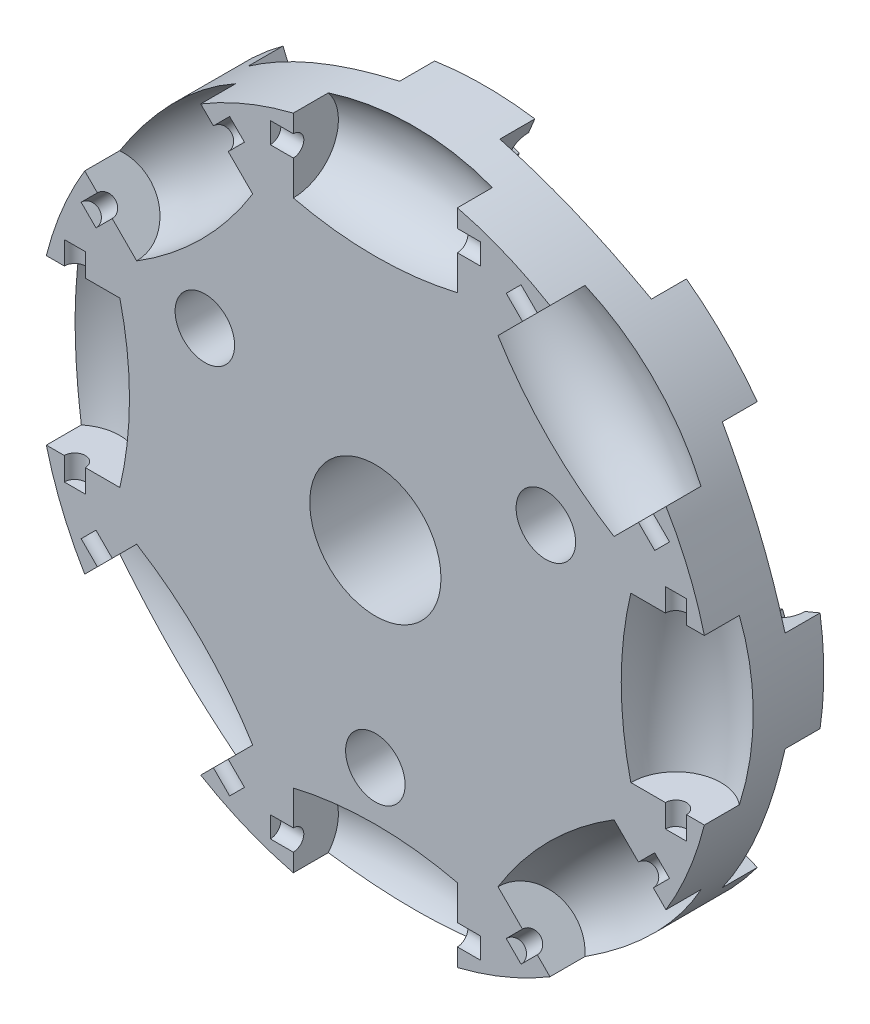
SolidWorks part; units mm, degrees
ref_plane "Front Plane" through (0, 0, 0) normal (0, 0, 1) x (1, 0, 0)
ref_plane "Top Plane" through (0, 0, 0) normal (0, 1, 0) x (1, 0, 0)
ref_plane "Right Plane" through (0, 0, 0) normal (1, 0, 0) x (0, 0, -1)
sketch "Sketch1" plane through (0, 0, 0) normal (0, 0, 1) x (1, 0, 0)
  circle A0 centre (0, 0) radius 24.6062
  point P11 (0, 0)
  dimension "D1" = 49.2125
extrude "Boss-Extrude1" add sketch "Sketch1" along normal mid plane 7.9375
ref_plane "Plane1" through (0, 0, 3.9688) normal (0, 0, 1) x (1, 0, 0)
ref_plane "Plane2" through (0, 0, -3.9688) normal (0, 0, 1) x (1, 0, 0)
sketch "Sketch5" plane through (0, 0, 3.9688) normal (0, 0, 1) x (1, 0, 0)
  line L0 (-5.9531, 25.0843) -> (-5.9531, 21.8122)
  line L1 (-5.9531, 21.8122) -> (5.9531, 21.8122)
  line L2 (5.9531, 21.8122) -> (5.9531, 25.0843)
  line L3 (-5.9531, 21.8122) -> (-8.0326, 21.8122) construction
  arc A2 (-5.9531, 25.0843) -> (5.9531, 25.0843) centre (0, 0) cw
  point P2 (0, 25.781)
  point P7 (0, 21.8122)
  dimension "D1" = 11.9062
  dimension "D2" = 7.9375
  dimension "D3" = 21.8122
revolve "Cut-Revolve5" cut sketch "Sketch5" angle 360 about L1
sketch "Sketch8" plane through (0, 0, -3.9688) normal (0, 0, 1) x (1, 0, 0)
  line L0 (4.0994, 25.453) -> (2.8472, 22.4301)
  line L1 (2.8472, 22.4301) -> (13.8472, 17.8737)
  line L2 (13.8472, 17.8737) -> (15.0993, 20.8967)
  line L3 (2.8472, 22.4301) -> (-2.3537, 24.5843) construction
  line L4 (0, 0) -> (9.4164, 22.7332) construction
  line L5 (0, 0) -> (0, 7.8748) construction
  arc A0 (4.0994, 25.453) -> (15.0993, 20.8967) centre (0, 0) cw
  arc A2 (-5.9531, 23.8753) -> (5.9531, 23.8753) centre (0, 0) ccw construction
  point P6 (8.3472, 20.1519)
  point P14 (9.866, 23.8185)
  dimension "D1" = 11.9062
  dimension "D2" = 7.9375
  dimension "D3" = 22.5
  dimension "D4" = 21.8122
revolve "Cut-Revolve6" cut sketch "Sketch8" angle 360 about L3
sketch "Sketch6" plane through (0, 0, 0) normal (1, 0, 0) x (0, 0, -1)
  arc A0 (-3.9688, 18.5402) -> (-1.429, 23.8753) centre (-3.9688, 21.8122) ccw construction
  circle A1 centre (-3.9688, 21.8122) radius 0.762
  point P4 (-3.9688, 21.8122)
  dimension "D1" = 1.524
extrude "Cut-Extrude2" cut sketch "Sketch6" against normal mid plane 15.24
ref_axis "Axis1" through (0, 0, -8.8615) along (0, 0, 1)
ref_plane "Plane3" through (0, 0, 0) normal (0.9239, -0.3827, 0) x (0, 0, -1)
sketch "Sketch10" plane through (0, 0, 0) normal (0.9239, -0.3827, 0) x (0, 0, -1)
  arc A1 (1.429, 23.8753) -> (3.9688, 18.5402) centre (3.9688, 21.8123) ccw construction
  circle A2 centre (3.9688, 21.8123) radius 0.889
  point P4 (3.9688, 21.8123)
  dimension "D1" = 1.778
extrude "Cut-Extrude3" cut sketch "Sketch10" against normal mid plane 15.875
pattern_circular "CirPattern1" count 8 over 360 about axis through (0, 0, 3.9688) along (0, 0, -1) of "Cut-Revolve5", "Cut-Revolve6", "Cut-Extrude2", "Cut-Extrude3"
sketch "Sketch16" plane through (0, 0, 3.9688) normal (0, 0, 1) x (1, 0, 0)
  circle A0 centre (0, -14.2875) radius 2.159
  circle A1 centre (-12.3733, 7.1437) radius 2.159
  circle A2 centre (12.3733, 7.1438) radius 2.159
  point P9 (0, 0)
  dimension "D1" = 4.318
  dimension "D2" = 14.2875
  dimension "D3" = 3
extrude "Cut-Extrude7" cut sketch "Sketch16" against normal through all
sketch "Sketch17" plane through (0, 0, 3.9688) normal (0, 0, 1) x (1, 0, 0)
  circle A0 centre (0, 0) radius 4.7625
  dimension "D1" = 9.525
extrude "Cut-Extrude8" cut sketch "Sketch17" against normal through all
